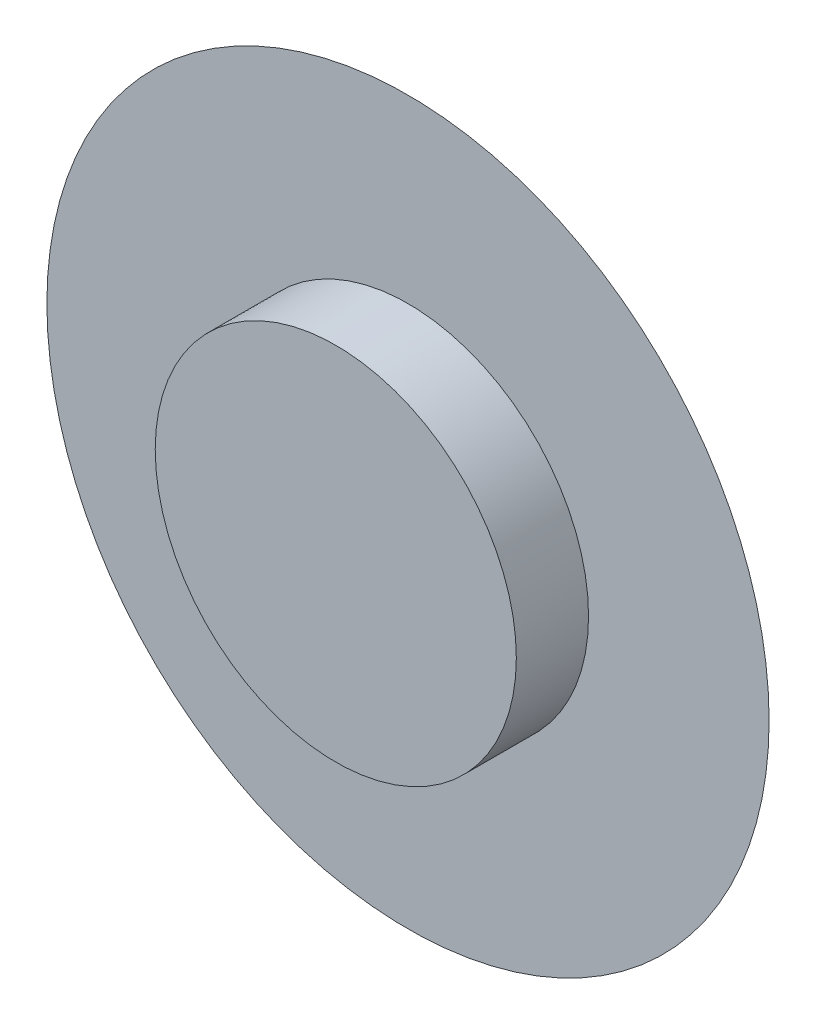
SolidWorks part; units mm, degrees
ref_plane "Front Plane" through (0, 0, 0) normal (0, 0, 1) x (1, 0, 0)
ref_plane "Top Plane" through (0, 0, 0) normal (0, 1, 0) x (1, 0, 0)
ref_plane "Right Plane" through (0, 0, 0) normal (1, 0, 0) x (0, 0, -1)
sketch "Sketch1" plane through (0, 0, 0) normal (0, 0, 1) x (1, 0, 0)
  circle A0 centre (0, 0) radius 5
  dimension "D1" = 10
extrude "Boss-Extrude1" add sketch "Sketch1" along normal blind 2
sketch "Sketch2" plane through (0, 0, 0) normal (0, 0, -1) x (-1, 0, 0)
  circle A0 centre (0, 0) radius 10
  dimension "D1" = 20
extrude "Boss-Extrude2" add sketch "Sketch2" along normal blind 1
fillet "Fillet1" radius 10 1 edges at (-10, 0, -1)
